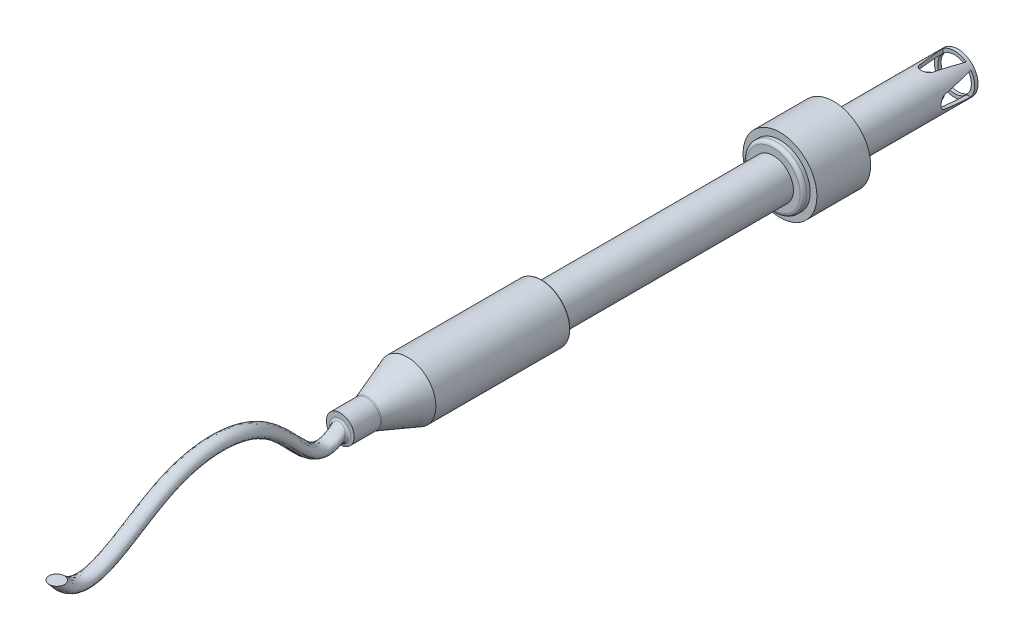
SolidWorks part; units mm, degrees
ref_plane "Alzado" through (0, 0, 0) normal (0, 0, 1) x (1, 0, 0)
ref_plane "Planta" through (0, 0, 0) normal (0, 1, 0) x (1, 0, 0)
ref_plane "Vista lateral" through (0, 0, 0) normal (1, 0, 0) x (0, 0, -1)
sketch "Croquis1" plane through (0, 0, 0) normal (0, 0, 1) x (1, 0, 0)
  circle A0 centre (0, 0) radius 11
  point P3 (0, 0)
  dimension "D1" = 22
extrude "Saliente-Extruir1" add sketch "Croquis1" along normal blind 16
sketch "Croquis2" plane through (0, 0, 16) normal (0, 0, 1) x (1, 0, 0)
  circle A0 centre (0, 0) radius 9
  dimension "D1" = 18
extrude "Saliente-Extruir2" add sketch "Croquis2" along normal blind 2
sketch "Croquis3" plane through (0, 0, 18) normal (0, 0, 1) x (1, 0, 0)
  circle A0 centre (0, 0) radius 6
  dimension "D1" = 12
extrude "Saliente-Extruir3" add sketch "Croquis3" along normal blind 69
sketch "Croquis4" plane through (0, 0, 87) normal (0, 0, 1) x (1, 0, 0)
  circle A0 centre (0, 0) radius 8.5
  dimension "D1" = 17
extrude "Saliente-Extruir4" add sketch "Croquis4" along normal blind 40
sketch "Croquis5" plane through (0, 0, 0) normal (0, 0, -1) x (-1, 0, 0)
  circle A0 centre (0, 0) radius 6
  dimension "D1" = 12
extrude "Saliente-Extruir5" add sketch "Croquis5" along normal blind 37
sketch "Croquis6" plane through (0, 0, 127) normal (0, 0, 1) x (1, 0, 0)
  circle A0 centre (0, 0) radius 8.5
  dimension "D1" = 17
extrude "Saliente-Extruir6" add sketch "Croquis6" along normal blind 12 draft 20
sketch "Croquis7" plane through (0, 0, 139) normal (0, 0, 1) x (1, 0, 0)
  circle A0 centre (0, 0) radius 4.1324
extrude "Saliente-Extruir7" add sketch "Croquis7" along normal blind 8
sketch "Croquis8" plane through (0, 0, 0) normal (1, 0, 0) x (0, 0, -1)
  line L0 (36, 3.5) -> (36, -3.5)
  line L2 (36, -3.5) -> (28, -2)
  line L3 (36, 3.5) -> (28, 2)
  line L4 (37, -6) -> (37, 6) construction
  line L5 (0, -6) -> (37, -6) construction
  arc A0 (28, 2) -> (28, -2) centre (28, 0) ccw
  point P2 (30.5374, 0.385)
  point P6 (31, 2.3386)
  point P8 (37, -3.2171)
  point P11 (0, 0)
  point P14 (28, 2)
  point P15 (28, -2)
  point P16 (0, 0)
  point P17 (0, 0)
  dimension "D1" = 8
  dimension "D2" = 2
  dimension "D3" = 7
  dimension "D4" = 1
  dimension "D5" = 2.5
extrude "Cortar-Extruir1" cut sketch "Croquis8" against normal through all both and the other way through all
sketch "Croquis9" plane through (0, 0, -37) normal (0, 0, -1) x (-1, 0, 0)
  circle A0 centre (0, 0) radius 5
  circle A1 centre (0, 0) radius 6 construction
  dimension "D1" = 1
extrude "Cortar-Extruir2" cut sketch "Croquis9" against normal blind 15 and the other way through all
sketch "Croquis10" plane through (0, 0, 0) normal (0, 1, 0) x (1, 0, 0)
  line L0 (3.5, 36) -> (-3.5, 36)
  line L1 (-3.5, 36) -> (-2, 28)
  line L5 (6, 37) -> (-6, 37) construction
  line L6 (-6, 37) -> (-6, 36) construction
  line L7 (3.5, 36) -> (2, 28)
  arc A1 (2, 28) -> (-2, 28) centre (0, 28) cw
  point P2 (1.753, 27.9746)
  point P5 (0, 0)
  point P6 (0, 0)
  point P11 (0, 0)
  point P12 (0, 0)
  dimension "D2" = 8
  dimension "D1" = 7
  dimension "D3" = 4
  dimension "D4" = 2.5
  dimension "D5" = 1
extrude "Cortar-Extruir3" cut sketch "Croquis10" against normal through all both and the other way through all
sketch "Croquis11" plane through (0, 0, -22) normal (0, 0, -1) x (-1, 0, 0)
  circle A0 centre (0, 0) radius 2.1489
extrude "Saliente-Extruir8" add sketch "Croquis11" along normal blind 4
sketch "Croquis12" plane through (0, 0, 0) normal (1, 0, 0) x (0, 0, -1)
  line L0 (25.0827, 0) -> (18.367, 0) construction
  line L1 (25.3446, 0.0124) -> (31.1759, 0.0124)
  arc A1 (25.3446, 0.0124) -> (31.1759, 0.0124) centre (28.2602, -0.694) ccw
  point P5 (28.211, -0.682)
  dimension "D1" = 3
revolve "Revolución9" add sketch "Croquis12" angle 360 about L1
sketch "Croquis13" plane through (0, 0, 0) normal (0, 0, -1) x (-1, 0, 0)
  circle A0 centre (0, 0.0124) radius 9.3196
  circle A1 centre (0, 0.0124) radius 5.9876
  circle M2 centre (0, 0) radius 6
extrude "Cortar-Extruir4" cut sketch "Croquis13" against normal blind 12 contours A0 M2 region at (9.056, 0.0124, 0)
sketch "Croquis15" plane through (0, 0, 147) normal (0, 0, 1) x (1, 0, 0)
  circle A0 centre (0, 0) radius 2.2722
sketch "Croquis16" plane through (0, 0, 0) normal (1, 0, 0) x (0, 0, -1)
  spline S0 degree 3 poles (-146.7016, 0) (-153.2305, -5.7459) (-160.3449, 2.8996) (-173.8391, 15.2718) (-201.7557, 16.0991) (-222.4712, -8.0568) (-231.7029, 3.1881) knots 0 0 0 0 0.196072 0.30221 0.595407 1 1 1 1
sweep "Barrer1" add profiles "Croquis15" path "Croquis16"
fillet "Redondeo1" radius 1 1 edges at (9, 0, 18)
fillet "Redondeo2" radius 0.2 1 edges at (8.5, 0, 87)
fillet "Redondeo3" radius 1 1 edges at (4.1324, 0, 139)
fillet "Redondeo4" radius 1 1 edges at (2.2722, 0, 147)
